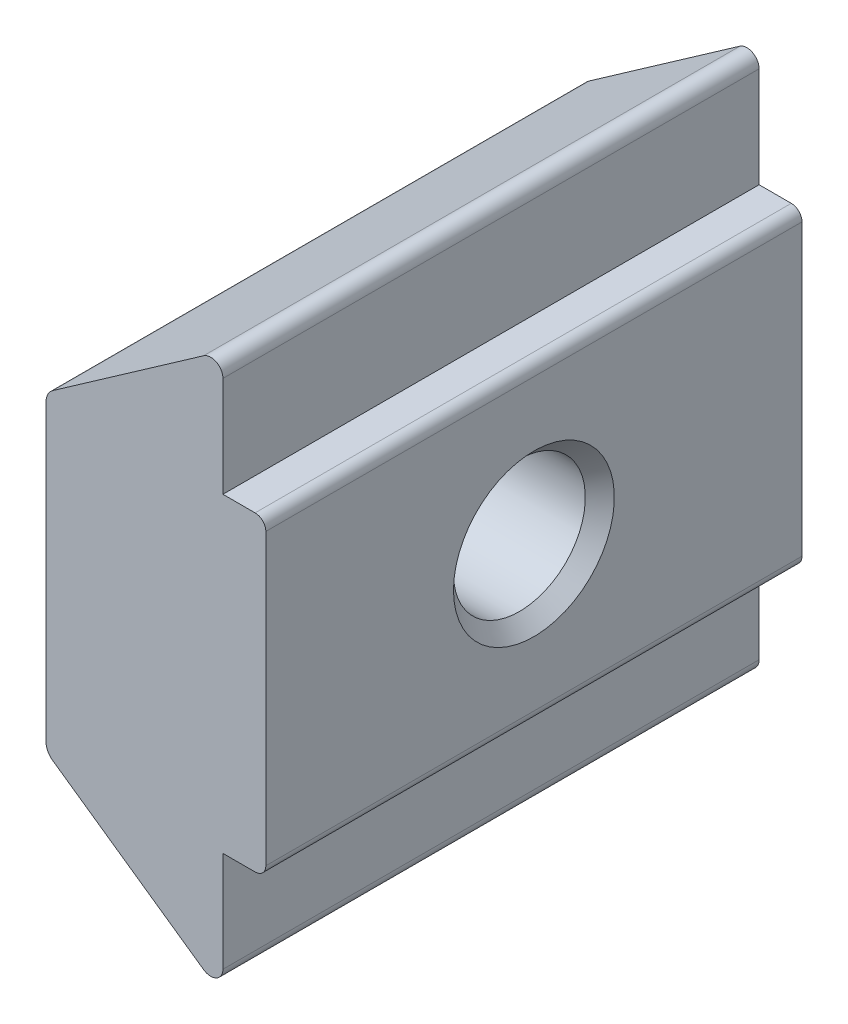
SolidWorks part; units mm, degrees
material "Alloy Steel"
ref_plane "Front Plane" through (0, 0, 0) normal (0, 0, 1) x (1, 0, 0)
ref_plane "Top Plane" through (0, 0, 0) normal (0, 1, 0) x (1, 0, 0)
ref_plane "Right Plane" through (0, 0, 0) normal (1, 0, 0) x (0, 0, -1)
ref_plane "Plane1" through (0, 0, 0) normal (0, 0, 1) x (1, 0, 0)
sketch "Sketch1" plane through (0, 0, 0) normal (0, 0, 1) x (1, 0, 0)
  line L0 (-3.972, -2.9896) -> (-1.1589, -4.9588)
  line L1 (-0.8, -4.7719) -> (-0.8, -2.9)
  line L2 (-0.8, -2.9) -> (-0.2, -2.9)
  line L3 (0, -2.7) -> (0, 2.7)
  line L4 (-0.2, 2.9) -> (-0.8, 2.9)
  line L5 (-0.8, 2.9) -> (-0.8, 4.7719)
  line L6 (-1.1589, 4.9588) -> (-3.972, 2.9896)
  line L7 (-4.1, 2.7438) -> (-4.1, -2.7438)
  arc A0 (-4.1, -2.7438) -> (-3.972, -2.9896) centre (-3.8, -2.7438) ccw
  arc A1 (-1.1589, -4.9588) -> (-0.8, -4.7719) centre (-1.0281, -4.7719) ccw
  arc A2 (-0.2, -2.9) -> (0, -2.7) centre (-0.2, -2.7) ccw
  arc A3 (0, 2.7) -> (-0.2, 2.9) centre (-0.2, 2.7) ccw
  arc A4 (-0.8, 4.7719) -> (-1.1589, 4.9588) centre (-1.0281, 4.7719) ccw
  arc A5 (-3.972, 2.9896) -> (-4.1, 2.7438) centre (-3.8, 2.7438) ccw
extrude "Boss-Extrude1" add sketch "Sketch1" against normal blind 5 and the other way blind 5
ref_plane "Plane2" through (0, 0, 0) normal (0, 0, 1) x (1, 0, 0)
sketch "Sketch2" plane through (0, 0, 0) normal (0, 0, 1) x (1, 0, 0)
  line L0 (-4.1, 0) -> (-4.1, 1.5)
  line L1 (-4.1, 1.5) -> (-3.8295, 1.2295)
  line L2 (-3.8295, 1.2295) -> (-0.2705, 1.2295)
  line L3 (-0.2705, 1.2295) -> (0, 1.5)
  line L4 (0, 1.5) -> (0, 0)
  line L5 (0, 0) -> (-4.1, 0)
  line L6 (0, 0) -> (-4.1, 0) construction
revolve "Cut-Revolve1" cut sketch "Sketch2" angle 360 about L6 reverse direction yes
